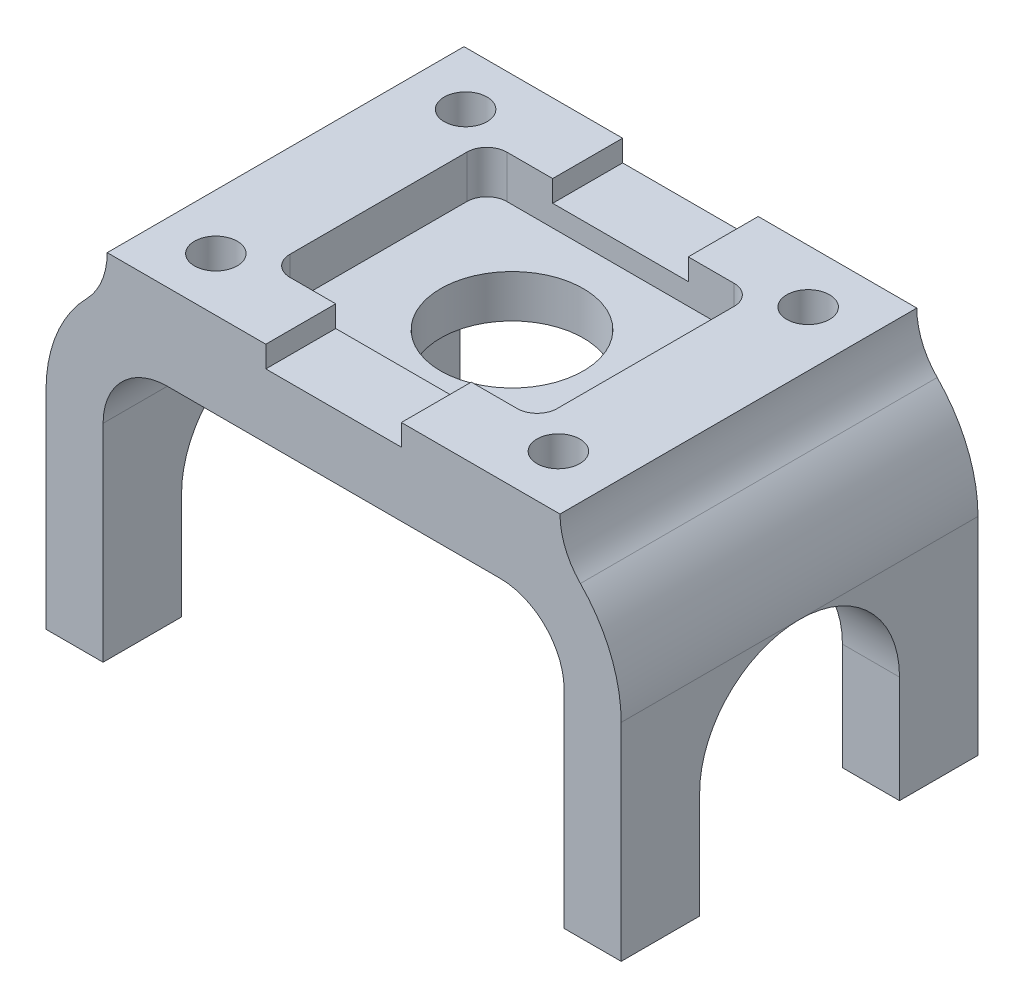
SolidWorks part; units mm, degrees
material "Plain Carbon Steel"
ref_plane "Front Plane" through (0, 0, 0) normal (0, 0, 1) x (1, 0, 0)
ref_plane "Top Plane" through (0, 0, 0) normal (0, 1, 0) x (1, 0, 0)
ref_plane "Right Plane" through (0, 0, 0) normal (1, 0, 0) x (0, 0, -1)
sketch "Sketch2" plane through (0, 0, 0) normal (0, 0, 1) x (1, 0, 0)
  line L0 (-29.591, 0) -> (29.591, 0)
  line L1 (41.021, -11.43) -> (41.021, -48.26)
  line L2 (41.021, -48.26) -> (51.181, -48.26)
  line L3 (51.181, -48.26) -> (51.181, -11.43)
  line L4 (40.2898, 15.24) -> (-40.2898, 15.24)
  line L5 (-51.181, -11.43) -> (-51.181, -48.26)
  line L6 (-51.181, -48.26) -> (-41.021, -48.26)
  line L7 (-41.021, -48.26) -> (-41.021, -11.43)
  line L8 (0, 0) -> (0, 94.6407) construction
  arc A0 (51.181, -11.43) -> (43.9202, 6.35) centre (25.781, -11.43) ccw
  arc A1 (43.9202, 6.35) -> (40.2898, 15.24) centre (52.9898, 15.24) cw
  arc A2 (-40.2898, 15.24) -> (-43.9202, 6.35) centre (-52.9898, 15.24) cw
  arc A3 (-43.9202, 6.35) -> (-51.181, -11.43) centre (-25.781, -11.43) ccw
  arc A4 (29.591, 0) -> (41.021, -11.43) centre (29.591, -11.43) cw
  arc A5 (-29.591, 0) -> (-41.021, -11.43) centre (-29.591, -11.43) ccw
  dimension "D1" = 36.83
  dimension "D4" = 12.7
  dimension "D5" = 25.4
  dimension "D2" = 10.16
  dimension "D3" = 15.24
  dimension "D6" = 82.042
  dimension "D7" = 63.5
extrude "Boss-Extrude1" add sketch "Sketch2" along normal mid plane 63.5
sketch "Sketch3" plane through (51.181, 0, 0) normal (1, 0, 0) x (0, 0, -1)
  line L0 (-17.78, -48.26) -> (17.78, -48.26)
  line L1 (-31.75, -48.26) -> (31.75, -48.26) construction
  line L2 (17.78, -48.26) -> (17.78, -29.21)
  line L3 (-17.78, -29.21) -> (-17.78, -48.26)
  line L4 (0, -48.26) -> (0, 0) construction
  arc A0 (17.78, -29.21) -> (-17.78, -29.21) centre (0, -29.21) ccw
  dimension "D1" = 19.05
  dimension "Cut_Width" = 35.56
extrude "Cut-Extrude1" cut sketch "Sketch3" against normal through all
sketch "Sketch4" plane through (0, 15.24, 0) normal (0, 1, 0) x (1, 0, 0)
  line L0 (40.2898, 31.75) -> (-40.2898, 31.75) construction
  line L1 (-20.2238, 19.304) -> (20.2238, 19.304)
  line L2 (-23.7798, 15.748) -> (-23.7798, -15.748)
  line L3 (-20.2238, -19.304) -> (20.2238, -19.304)
  line L4 (23.7798, 15.748) -> (23.7798, -15.748)
  line L5 (-23.7798, -19.304) -> (23.7798, 19.304) construction
  line L6 (-40.2898, -31.75) -> (-40.2898, 31.75) construction
  arc A0 (-23.7798, -15.748) -> (-20.2238, -19.304) centre (-20.2238, -15.748) ccw
  arc A1 (20.2238, -19.304) -> (23.7798, -15.748) centre (20.2238, -15.748) ccw
  arc A2 (20.2238, 19.304) -> (23.7798, 15.748) centre (20.2238, 15.748) cw
  arc A3 (-20.2238, 19.304) -> (-23.7798, 15.748) centre (-20.2238, 15.748) ccw
  dimension "D3" = 3.556
  dimension "D1" = 12.446
  dimension "D2" = 16.51
extrude "Cut-Extrude2" cut sketch "Sketch4" against normal blind 7.62
sketch "Sketch5" plane through (0, 0, 31.75) normal (0, 0, 1) x (1, 0, 0)
  line L0 (0, 0) -> (0, 29.0489) construction
  line L1 (-29.591, 0) -> (29.591, 0) construction
  line L2 (40.2898, 15.24) -> (-40.2898, 15.24) construction
  line L3 (12.065, 15.24) -> (-12.065, 15.24)
  line L4 (12.065, 15.24) -> (12.065, 11.43)
  line L5 (12.065, 11.43) -> (-12.065, 11.43)
  line L6 (-12.065, 15.24) -> (-12.065, 11.43)
  dimension "D1" = 24.13
  dimension "D2" = 3.81
extrude "Cut-Extrude3" cut sketch "Sketch5" against normal through all
sketch "Sketch6" plane through (0, 7.62, 0) normal (0, 1, 0) x (1, 0, 0)
  circle A0 centre (0, 0) radius 12.7
  dimension "Hole_Diameter" = 25.4
extrude "Cut-Extrude4" cut sketch "Sketch6" against normal up to next
sketch "Sketch7" plane through (0, 15.24, 0) normal (0, 1, 0) x (1, 0, 0)
  line L0 (-57.8306, 0) -> (65.0092, 0) construction
  line L1 (0, -38.3252) -> (0, 42.5913) construction
  circle A0 centre (-30.48, 22.225) radius 3.81
  circle A1 centre (30.48, 22.225) radius 3.81
  circle A2 centre (30.48, -22.225) radius 3.81
  circle A3 centre (-30.48, -22.225) radius 3.81
  dimension "D1" = 7.62
  dimension "D2" = 60.96
  dimension "D3" = 44.45
extrude "Cut-Extrude5" cut sketch "Sketch7" against normal up to next
